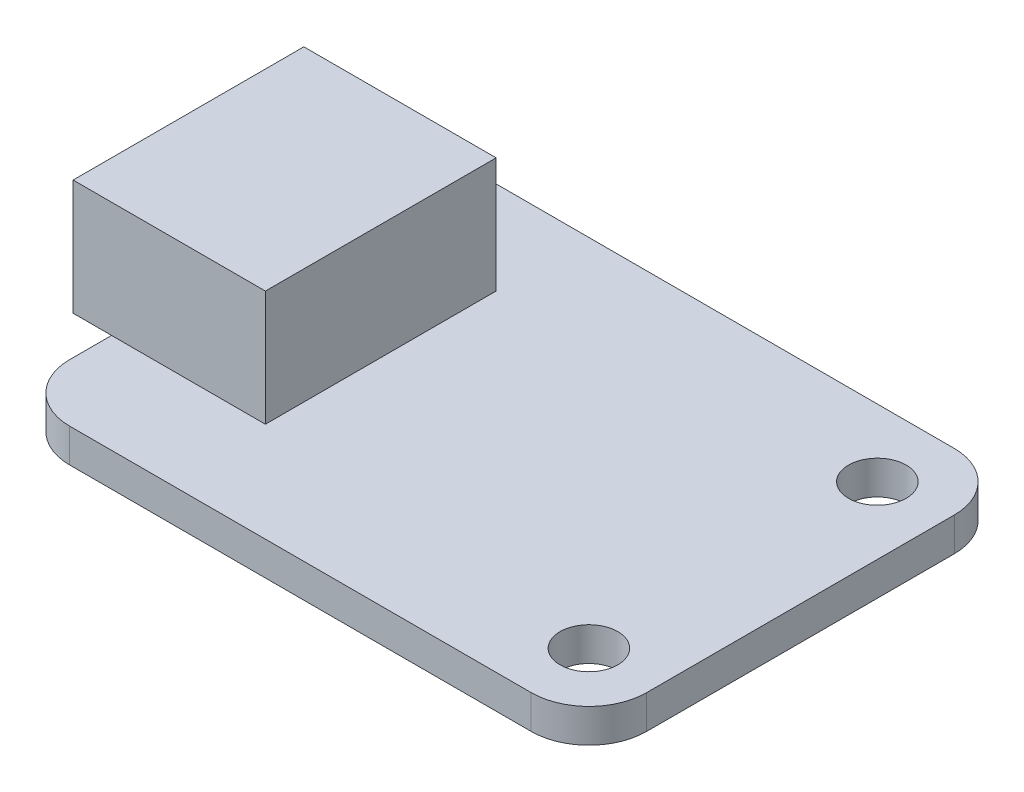
SolidWorks part; units mm, degrees
ref_plane "Front" through (0, 0, 0) normal (0, 0, 1) x (1, 0, 0)
ref_plane "Top" through (0, 0, 0) normal (0, 1, 0) x (1, 0, 0)
ref_plane "Side" through (0, 0, 0) normal (1, 0, 0) x (0, 0, -1)
ref_axis "X_Axis" through (-20.1896, 0, 0) along (1, 0, 0)
ref_axis "Y_Axis" through (0, -14.8261, 0) along (0, 1, 0)
ref_axis "Z_Axis" through (0, 0, -19.842) along (0, 0, 1)
sketch "Sketch1" plane through (0, 0, 0) normal (0, 1, 0) x (1, 0, 0)
  line L0 (15, 0) -> (-15, 0) construction
  line L1 (12, 11) -> (-12, 11)
  line L2 (15, 8) -> (15, -8)
  line L3 (12, -11) -> (-12, -11)
  line L4 (-15, 8) -> (-15, -8)
  line L5 (15, 11) -> (-15, -11) construction
  line L6 (15, -11) -> (-15, 11) construction
  circle A0 centre (11.5, 7.5) radius 1.5
  circle A1 centre (11.5, -7.5) radius 1.5
  arc A2 (-12, -11) -> (-15, -8) centre (-12, -8) cw
  arc A3 (-12, 11) -> (-15, 8) centre (-12, 8) ccw
  arc A4 (15, -8) -> (12, -11) centre (12, -8) cw
  arc A5 (12, 11) -> (15, 8) centre (12, 8) cw
  point P0 (0, 0)
  dimension "D3" = 3
  dimension "D6" = 3
  dimension "D1" = 30
  dimension "D2" = 22
  dimension "D4" = 15
  dimension "D5" = 3.5
extrude "Boss-Extrude1" add sketch "Sketch1" along normal blind 1.75
sketch "Sketch2" plane through (0, 1.75, 0) normal (0, 1, 0) x (1, 0, 0)
  line L0 (-15, 8) -> (-15, -8) construction
  line L1 (-7, 6.1749) -> (-17, 6.1749)
  line L2 (-7, 6.1749) -> (-7, -5.8251)
  line L3 (-7, -5.8251) -> (-17, -5.8251)
  line L4 (-17, 6.1749) -> (-17, -5.8251)
  line L5 (-7, 6.1749) -> (-17, -5.8251) construction
  line L6 (-7, -5.8251) -> (-17, 6.1749) construction
  point P0 (-12, 0.1749)
  dimension "D1" = 12
  dimension "D2" = 2
  dimension "D3" = 10
extrude "Boss-Extrude2" add sketch "Sketch2" along normal blind 6
